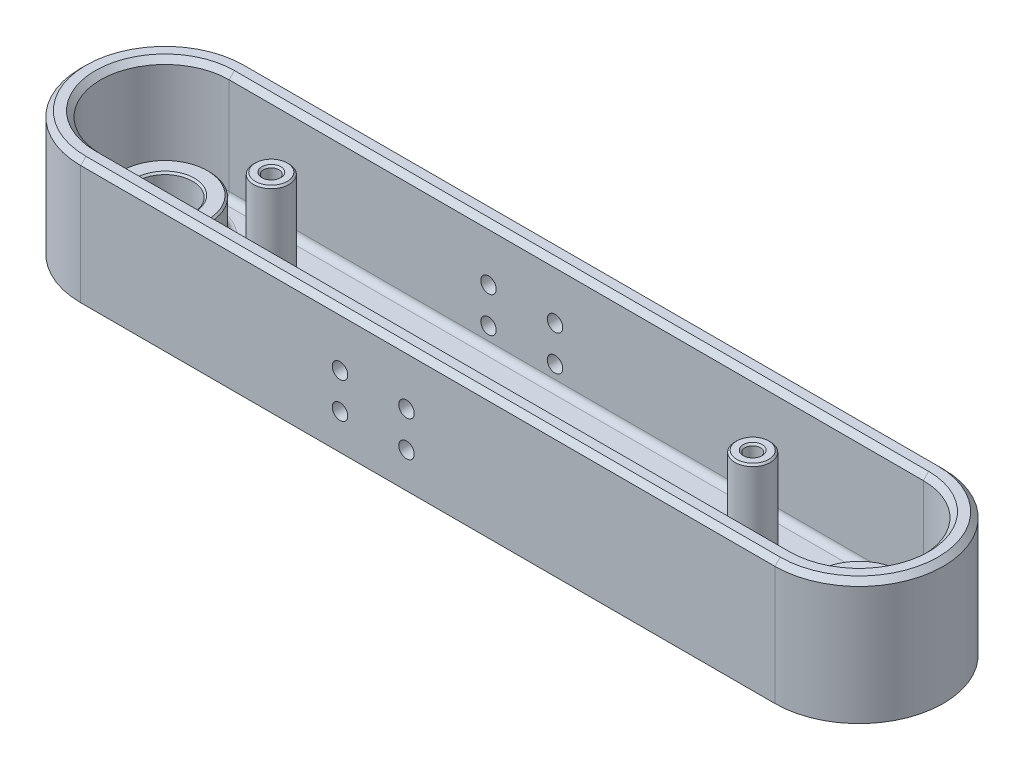
SolidWorks part; units mm, degrees
material "PLA"
ref_plane "Front Plane" through (0, 0, 0) normal (0, 0, 1) x (1, 0, 0)
ref_plane "Top Plane" through (0, 0, 0) normal (0, 1, 0) x (1, 0, 0)
ref_plane "Right Plane" through (0, 0, 0) normal (1, 0, 0) x (0, 0, -1)
sketch "Sketch1" plane through (0, 0, 0) normal (0, 1, 0) x (1, 0, 0)
  line L0 (-99.441, 0) -> (99.441, 0) construction
  line L1 (0, -55.9739) -> (0, 55.9739) construction
  line L2 (-99.441, 24.13) -> (99.441, 24.13)
  line L3 (-99.441, -24.13) -> (99.441, -24.13)
  arc A0 (-99.441, 24.13) -> (-99.441, -24.13) centre (-99.441, 0) ccw
  arc A1 (99.441, 24.13) -> (99.441, -24.13) centre (99.441, 0) cw
  point P4 (0, 0)
  point P10 (0, 0)
  dimension "D2" = 48.26
  dimension "D1" = 198.882
extrude "MainBlock" add sketch "Sketch1" along normal blind 35.56
sketch "Sketch2" plane through (0, 35.56, 0) normal (0, 1, 0) x (1, 0, 0)
  line L0 (0, 0) -> (155.7407, 0) construction
  line L1 (0, 0) -> (0, 57.4416) construction
  line L2 (-99.441, -24.13) -> (99.441, -24.13) construction
  line L3 (99.441, 24.13) -> (-99.441, 24.13) construction
  line L4 (-99.441, -24.13) -> (99.441, -24.13) construction
  line L5 (99.441, 24.13) -> (-99.441, 24.13) construction
  line L6 (-99.441, 18.415) -> (99.441, 18.415)
  line L7 (-99.441, -18.415) -> (99.441, -18.415)
  arc A0 (99.441, -24.13) -> (99.441, 24.13) centre (99.441, 0) ccw construction
  arc A1 (-99.441, 24.13) -> (-99.441, -24.13) centre (-99.441, 0) ccw construction
  arc A2 (99.441, -24.13) -> (99.441, 24.13) centre (99.441, 0) ccw construction
  arc A3 (-99.441, 24.13) -> (-99.441, -24.13) centre (-99.441, 0) ccw construction
  arc A4 (-99.441, 18.415) -> (-99.441, -18.415) centre (-99.441, 0) ccw
  arc A5 (99.441, 18.415) -> (99.441, -18.415) centre (99.441, 0) cw
  point P18 (0, 18.415)
  point P19 (0, -18.415)
  dimension "D1" = 5.715
extrude "MainPocket" cut sketch "Sketch2" against normal offset from surface (31.115 mm away) 4.445 up to face at (0, 0, 0)
sketch "Sketch3" plane through (0, 0, 0) normal (0, -1, 0) x (1, 0, 0)
  line L2 (-99.441, -24.13) -> (99.441, -24.13)
  line L3 (99.441, 24.13) -> (-99.441, 24.13)
  line L4 (-99.441, -24.13) -> (99.441, -24.13) construction
  line L5 (99.441, 24.13) -> (-99.441, 24.13) construction
  circle A0 centre (-99.441, 0) radius 4.445
  circle A1 centre (99.441, 0) radius 4.445
  arc A2 (-99.441, 24.13) -> (-99.441, -24.13) centre (-99.441, 0) ccw
  arc A3 (99.441, -24.13) -> (99.441, 24.13) centre (99.441, 0) ccw
  arc A4 (-99.441, 24.13) -> (-99.441, -24.13) centre (-99.441, 0) ccw construction
  arc A5 (99.441, -24.13) -> (99.441, 24.13) centre (99.441, 0) ccw construction
  dimension "D2" = 8.89
  dimension "D3" = 8.89
  dimension "D1" = 0
extrude "Cut-Extrude1" cut sketch "Sketch3" against normal through all
sketch "Sketch4" plane through (0, 4.445, 0) normal (0, 1, 0) x (1, 0, 0)
  line L0 (0, 0) -> (50000, 0) construction
  line L1 (0, 0) -> (0, 50000) construction
  line L2 (99.441, 18.415) -> (-99.441, 18.415)
  line L3 (-99.441, -18.415) -> (99.441, -18.415)
  line L4 (99.441, 18.415) -> (-99.441, 18.415) construction
  line L5 (-99.441, -18.415) -> (99.441, -18.415) construction
  circle A0 centre (-99.441, 0) radius 7.9566
  circle A1 centre (-99.441, 0) radius 12.7
  arc A2 (99.441, -18.415) -> (99.441, 18.415) centre (99.441, 0) ccw
  arc A3 (-99.441, 18.415) -> (-99.441, -18.415) centre (-99.441, 0) ccw
  arc A4 (99.441, -18.415) -> (99.441, 18.415) centre (99.441, 0) ccw construction
  arc A5 (-99.441, 18.415) -> (-99.441, -18.415) centre (-99.441, 0) ccw construction
  circle A6 centre (99.441, 0) radius 12.7
  circle A7 centre (99.441, 0) radius 7.9566
  dimension "D2" = 15.9131
  dimension "D3" = 25.4
  dimension "D1" = 0
extrude "Bearing-Housing" add sketch "Sketch4" along normal blind 10.16
sketch "Sketch5" plane through (0, 0, 0) normal (0, -1, 0) x (1, 0, 0)
  line L0 (0, 0) -> (0, 50000) construction
  line L2 (-99.441, -24.13) -> (99.441, -24.13)
  line L3 (99.441, 24.13) -> (-99.441, 24.13)
  line L4 (-99.441, -24.13) -> (99.441, -24.13) construction
  line L5 (99.441, 24.13) -> (-99.441, 24.13) construction
  circle A0 centre (-99.441, 0) radius 6.35
  circle A1 centre (-99.441, 0) radius 4.445 construction
  arc A2 (-99.441, 24.13) -> (-99.441, -24.13) centre (-99.441, 0) ccw
  arc A3 (99.441, -24.13) -> (99.441, 24.13) centre (99.441, 0) ccw
  arc A4 (-99.441, 24.13) -> (-99.441, -24.13) centre (-99.441, 0) ccw construction
  arc A5 (99.441, -24.13) -> (99.441, 24.13) centre (99.441, 0) ccw construction
  circle A6 centre (-99.441, 0) radius 4.445
  circle A7 centre (99.441, 0) radius 4.445 construction
  circle A8 centre (99.441, 0) radius 6.35 construction
  dimension "D2" = 12.7
  dimension "D1" = 0
extrude "Boss-Extrude2" [suppressed] add sketch "Sketch5" along normal blind 3.81
fillet "Fillet1" [suppressed] radius 1.27
sketch "Sketch7" plane through (0, 4.445, 0) normal (0, 1, 0) x (1, 0, 0)
  line L0 (1.3556, 0) -> (50001.3556, 0) construction
  circle A0 centre (0, 0) radius 2.2225 construction
  circle A1 centre (-68.961, 0) radius 2.2225
  circle A2 centre (-99.441, 0) radius 4.445 construction
  circle A3 centre (99.441, 0) radius 4.445 construction
  circle A4 centre (99.441, 0) radius 4.445 construction
  circle A5 centre (-99.441, 0) radius 4.445 construction
  circle A6 centre (68.961, 0) radius 2.2225
  circle A7 centre (-68.961, 0) radius 5.08
  circle A8 centre (0, 0) radius 5.08 construction
  circle A9 centre (68.961, 0) radius 5.08
  dimension "D3" = 4.445
  dimension "D4" = 4.445
  dimension "D5" = 4.445
  dimension "D6" = 10.16
  dimension "D7" = 10.16
  dimension "D8" = 10.16
  dimension "D1" = 30.48
  dimension "D2" = 30.48
extrude "Boss-Extrude3" add sketch "Sketch7" along normal up to surface (31.115 mm away) up to face at (0, 35.56, 0)
fillet "Fillet2" radius 0.635 2 edges at (99.441, 4.445, 7.9566) (-99.441, 4.445, 7.9566)
fillet "Fillet3" radius 1.905 6 edges at (117.856, 4.445, 0) (0, 4.445, 18.415) (-117.856, 4.445, 0) (99.441, 4.445, -12.7) (-99.441, 4.445, 12.7) (0, 4.445, -18.415)
fillet "Fillet6" radius 4.445 2 edges at (68.961, 4.445, 5.08) (-68.961, 4.445, 5.08)
sketch "Sketch9" plane through (0, 0, 0) normal (0, -1, 0) x (1, 0, 0)
  circle A0 centre (99.441, 0) radius 4.445 construction
  circle A1 centre (99.441, 0) radius 4.445
  circle A6 centre (99.441, 0) radius 5.715
  dimension "D2" = 11.43
extrude "Bearing-Spacer" [suppressed] add sketch "Sketch9" along normal blind 8.89
fillet "Fillet7" [suppressed] radius 2.54
chamfer "Chamfer1" [suppressed] distance 0.508 angle 45
chamfer "Chamfer2" distance 0.508 angle 45 10 edges at (68.961, 35.56, 2.2225) (99.441, 4.445, 4.445) (99.441, 14.605, -12.7) (99.441, 14.605, -7.9566) (-99.441, 4.445, 4.445) (-99.441, 14.605, 12.7) (-68.961, 35.56, 5.08) (68.961, 35.56, 5.08) (-99.441, 14.605, 7.9566) (-68.961, 35.56, 2.2225)
sketch "Sketch12" plane through (0, 0, 0) normal (0, 1, 0) x (1, 0, 0)
  line L0 (-34.671, 24.13) -> (-24.511, 35.56)
  line L1 (99.441, 24.13) -> (-99.441, 24.13) construction
  line L2 (-18.161, 29.21) -> (-18.161, 24.13) construction
  line L3 (-24.511, 35.56) -> (-11.811, 35.56)
  line L4 (-34.671, 24.13) -> (-1.651, 24.13)
  line L5 (-1.651, 24.13) -> (-11.811, 35.56)
  circle A0 centre (-18.161, 29.21) radius 2.0066
  circle A1 centre (-99.441, 0) radius 4.445 construction
  point P9 (-18.161, 35.56)
  dimension "D5" = 4.0132
  dimension "D1" = 33.02
  dimension "D2" = 12.7
  dimension "D3" = 29.21
  dimension "D4" = 11.43
  dimension "D6" = 81.28
extrude "Stab_bar_Mount" [suppressed] add sketch "Sketch12" along normal blind 25.4
chamfer "Chamfer3" distance 1.524 angle 45 8 edges at (0, 35.56, -24.13) (-123.571, 35.56, 0) (123.571, 35.56, 0) (0, 35.56, 24.13) (0, 35.56, -18.415) (-117.856, 35.56, 0) (117.856, 35.56, 0) (0, 35.56, 18.415)
chamfer "Chamfer5" [suppressed] distance 0.381 angle 45
sketch "Sketch10" plane through (0, 4.445, 0) normal (0, 1, 0) x (1, 0, 0)
  circle A0 centre (68.961, 0) radius 2.2225 construction
  circle A2 centre (-68.961, 0) radius 2.2225 construction
  circle A3 centre (68.961, 0) radius 2.2225
  circle A4 centre (0, 0) radius 2.2225 construction
  circle A5 centre (-68.961, 0) radius 2.2225
extrude "Boss-Extrude4" add sketch "Sketch10" along normal blind 16.51
fillet "Fillet8" [suppressed] radius 5.08
sketch "Sketch13" plane through (0, 0, -24.13) normal (0, 0, -1) x (-1, 0, 0)
  line L0 (6.096, 20.32) -> (25.146, 20.32) construction
  line L1 (25.146, 20.32) -> (25.146, 10.16) construction
  line L2 (25.146, 10.16) -> (6.096, 10.16) construction
  line L3 (6.096, 10.16) -> (6.096, 20.32) construction
  line L4 (15.621, 20.32) -> (15.621, 10.16) construction
  line L5 (6.096, 15.24) -> (25.146, 15.24) construction
  line L6 (-99.441, 0) -> (99.441, 0) construction
  line L7 (99.441, 34.036) -> (99.441, 0) construction
  circle A0 centre (25.146, 20.32) radius 2.2225
  circle A1 centre (6.096, 20.32) radius 2.2225
  circle A2 centre (6.096, 10.16) radius 2.2225
  circle A3 centre (25.146, 10.16) radius 2.2225
  dimension "D3" = 4.445
  dimension "D1" = 19.05
  dimension "D2" = 10.16
  dimension "D4" = 15.24
  dimension "D5" = 83.82
extrude "Stabilizer-Bar-MountHoles" cut sketch "Sketch13" against normal up to surface (5.715 mm away) up to face at (0, 20.193, -18.415)
mirror "Mirror1" about plane through (0, 0, 0) normal (0, 0, 1) of "Stabilizer-Bar-MountHoles"
equation "\"D5@Sketch7\"=\"D3@Sketch7\""
equation "\"D4@Sketch7\"=\"D3@Sketch7\""
equation "\"D7@Sketch7\"=\"D6@Sketch7\""
equation "\"D8@Sketch7\"=\"D6@Sketch7\""
